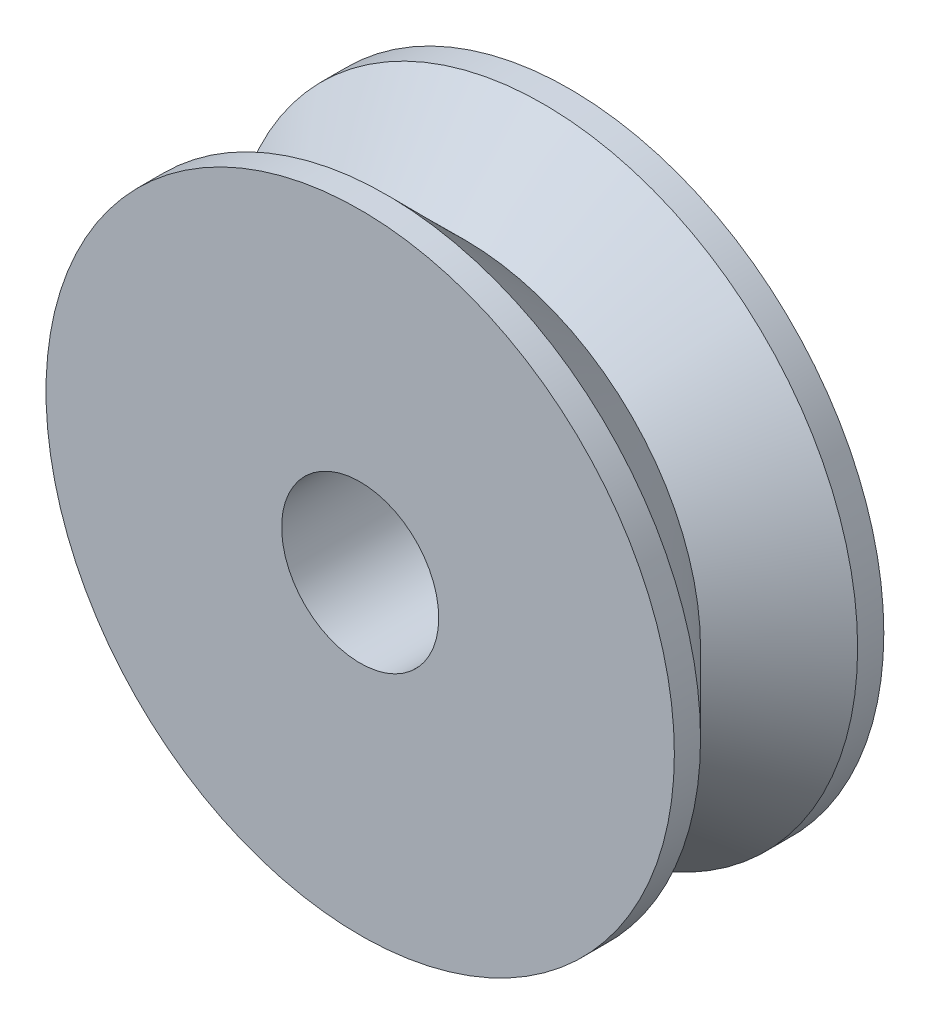
SolidWorks part; units mm, degrees
ref_plane "Front Plane" through (0, 0, 0) normal (0, 0, 1) x (1, 0, 0)
ref_plane "Top Plane" through (0, 0, 0) normal (0, 1, 0) x (1, 0, 0)
ref_plane "Right Plane" through (0, 0, 0) normal (1, 0, 0) x (0, 0, -1)
sketch "Sketch1" plane through (0, 0, 0) normal (0, 0, 1) x (1, 0, 0)
  circle A0 centre (0, 0) radius 6
  circle A1 centre (0, 0) radius 1.5
  dimension "D1" = 3
  dimension "D2" = 12
extrude "Boss-Extrude1" add sketch "Sketch1" along normal blind 2
chamfer "Chamfer1" distance 1.5 angle 45 1 edges at (6, 0, 2)
sketch "Sketch2" plane through (0, 0, 2) normal (0, 0, 1) x (1, 0, 0)
  circle A0 centre (0, 0) radius 6
  circle A1 centre (0, 0) radius 1.5
  circle A2 centre (0, 0) radius 4.5 construction
  dimension "D1" = 3
  dimension "D2" = 12
extrude "Boss-Extrude2" add sketch "Sketch2" along normal blind 2
chamfer "Chamfer2" distance 1.5 angle 45 1 edges at (6, 0, 2)
